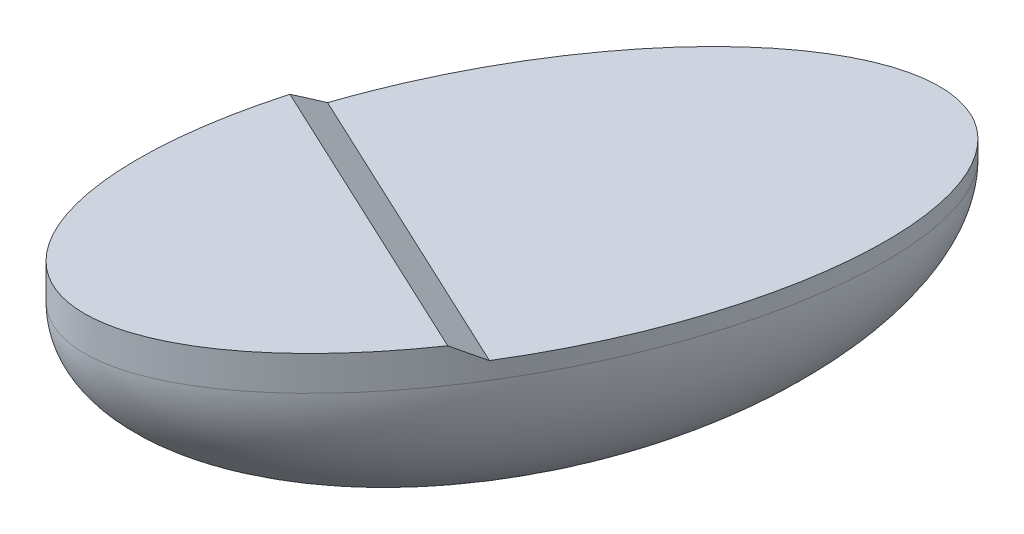
SolidWorks part; units mm, degrees
ref_plane "Front Plane" through (0, 0, 0) normal (0, 0, 1) x (1, 0, 0)
ref_plane "Top Plane" through (0, 0, 0) normal (0, 1, 0) x (1, 0, 0)
ref_plane "Right Plane" through (0, 0, 0) normal (1, 0, 0) x (0, 0, -1)
sketch "Sketch1" plane through (0, 0, 0) normal (0, 1, 0) x (1, 0, 0)
  ellipse E0 centre (0, 0) end of major axis (16957.6042, 36227.6091) minor radius 20000
extrude "Boss-Extrude1" add sketch "Sketch1" along normal blind 2000
sketch "Sketch2" plane through (0, 0, 0) normal (0, -1, 0) x (1, 0, 0)
  line L0 (-16957.6042, 36227.6091) -> (16957.6042, -36227.6091)
  ellipse E0 centre (0, 0) end of major axis (16957.6042, -36227.6091) minor radius 20000 construction
  ellipse E2 centre (0, 0) end of major axis (16957.6042, -36227.6091) minor radius 20000
  ellipse E3 centre (0, 0) end of major axis (16957.6042, -36227.6091) minor radius 20000 (16957.6042, -36227.6091) -> (-16957.6042, 36227.6091) ccw
  dimension "D1" = 0
revolve "Revolve1" add sketch "Sketch2" angle 180 about L0
sketch "Sketch3" plane through (0, 2000, 0) normal (0, 1, 0) x (1, 0, 0)
  line L0 (-16957.6042, -36227.6091) -> (16957.6042, 36227.6091) construction
  line L1 (-21472.6802, 86.6304) -> (13820.8411, -16433.7413)
  ellipse E1 centre (0, 0) end of major axis (16957.6042, 36227.6091) minor radius 20000
  ellipse E2 centre (0, 0) end of major axis (16957.6042, 36227.6091) minor radius 20000
  ellipse M4 centre (0, 0) end of major axis (16957.6042, 36227.6091) minor radius 20000
  dimension "D2" = 90
  dimension "D1" = 0
extrude "Boss-Extrude2" add sketch "Sketch3" along normal blind 2000 contours L0 L1 M4 | L0 E2 L1 region at (-16477.7018, 2000, 16520.3329) region at (-2131.4567, 2000, 23235.5966)
chamfer "Chamfer1" distance 2000 angle 60 1 edges at (-3825.9196, 4000, 8173.5554) first distance on face at (-3825.9196, 3000, 8173.5554)
